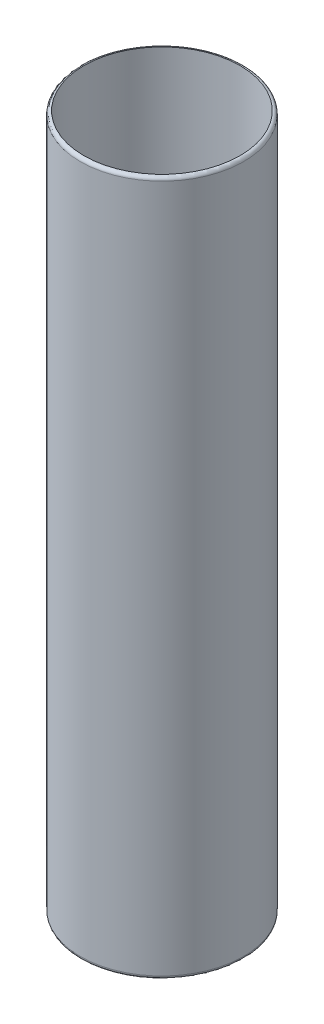
SolidWorks part; units mm, degrees
ref_plane "Alzado" through (0, 0, 0) normal (0, 0, 1) x (1, 0, 0)
ref_plane "Planta" through (0, 0, 0) normal (0, 1, 0) x (1, 0, 0)
ref_plane "Vista lateral" through (0, 0, 0) normal (1, 0, 0) x (0, 0, -1)
sketch "Croquis1" plane through (0, 0, 0) normal (0, 1, 0) x (1, 0, 0)
  circle A0 centre (0, 0) radius 11.73
  dimension "D1" = 23.46
extrude "Saliente-Extruir1" add sketch "Croquis1" along normal blind 100
sketch "Croquis2" plane through (0, 100, 0) normal (0, 1, 0) x (1, 0, 0)
  circle A0 centre (0, 0) radius 11.23
  dimension "D1" = 22.46
extrude "Cortar-Extruir1" cut sketch "Croquis2" against normal through all
fillet "Redondeo1" radius 0.5 1 edges at (0, 100, 11.73)
fillet "Redondeo4" radius 0.5 1 edges at (0, 0, 11.73)
